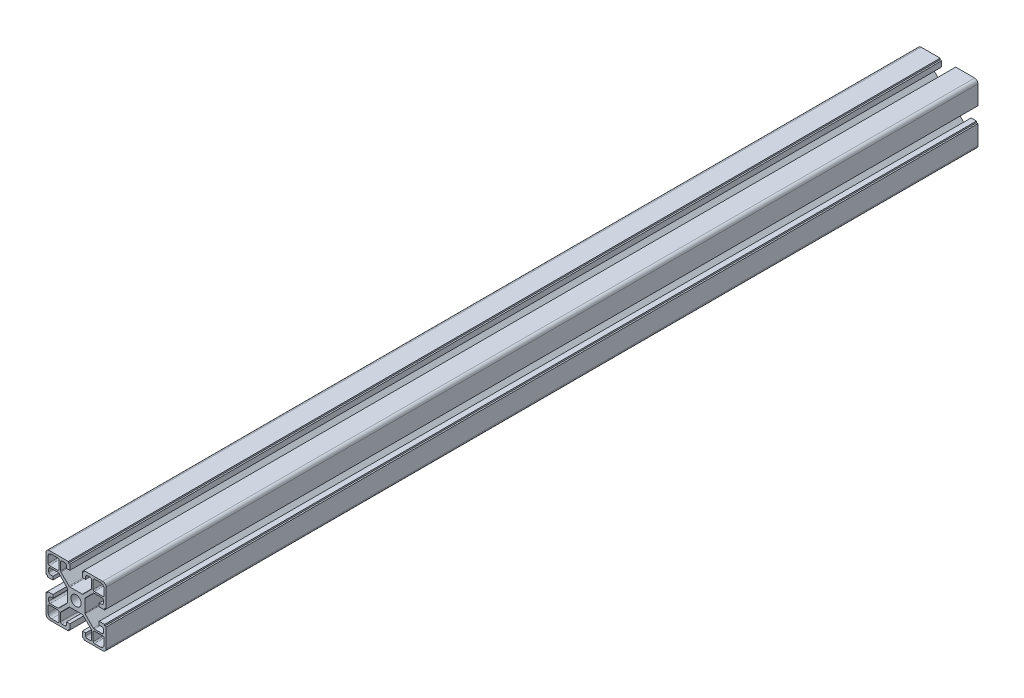
SolidWorks part; units mm, degrees
material "6063-T5"
ref_plane "Front Plane" through (0, 0, 0) normal (0, 0, 1) x (1, 0, 0)
ref_plane "Top Plane" through (0, 0, 0) normal (0, 1, 0) x (1, 0, 0)
ref_plane "Right Plane" through (0, 0, 0) normal (1, 0, 0) x (0, 0, -1)
sketch "Sketch1" plane through (0, 0, 0) normal (0, 0, 1) x (1, 0, 0)
  line L4 (20, 17.75) -> (20, 5.15)
  line L5 (0, -17.7813) -> (0, 18.2) construction
  line L6 (0, 0) -> (38.8613, 0) construction
  line L8 (18.6, 16.35) -> (18.6, 12.2)
  line L10 (11.4, 17.8) -> (11.4, 12.2)
  line L11 (-4.1, 5.85) -> (4.1, 5.85)
  line L14 (5.85, 4.1089) -> (5.85, -4.1089)
  line L17 (12.2, 11.4) -> (17.8, 11.4)
  line L24 (4.15, 19) -> (4.15, 15.4)
  line L25 (4.15, 15.4) -> (6.35, 15.4)
  line L26 (6.35, 15.4) -> (6.35, 16.95)
  line L27 (10.3, 17.2) -> (10.3, 12.0545)
  line L28 (10.0659, 11.489) -> (4.6659, 6.0845)
  line L29 (6.0841, 4.6743) -> (11.4708, 10.0655)
  line L30 (12.0367, 10.3) -> (17.2, 10.3)
  line L31 (18.2, 9.3) -> (18.2, 7.6)
  line L32 (16.95, 6.35) -> (15.4, 6.35)
  line L33 (15.4, 6.35) -> (15.4, 4.15)
  line L34 (15.4, 4.15) -> (19, 4.15)
  line L35 (18.6, 18.6) -> (18.6, -18.6) construction
  line L36 (-18.6, 18.6) -> (18.6, 18.6) construction
  line L37 (-20, 20) -> (20, 20) construction
  line L38 (20, 20) -> (20, -20) construction
  line L40 (7.6, 18.2) -> (9.3, 18.2)
  line L42 (4.15, 19) -> (5.15, 19)
  line L43 (5.15, 19) -> (5.15, 20)
  line L56 (-18.6, 18.6) -> (-18.6, -18.6) construction
  line L57 (-20, 20) -> (-20, -20) construction
  line L60 (5.15, 20) -> (17.75, 20)
  line L91 (-18.6, -18.6) -> (18.6, -18.6) construction
  line L92 (-20, -20) -> (20, -20) construction
  line L93 (12.2, 18.6) -> (16.35, 18.6)
  line L94 (17.9399, 17.9421) -> (20, 20) construction
  line L95 (0, 0) -> (11.4, 11.4094) construction
  line L101 (19, 4.15) -> (19, 5.15)
  line L102 (19, 5.15) -> (20, 5.15)
  line L104 (-5.85, 4.1089) -> (-5.85, -4.1089)
  line L105 (-19, 5.15) -> (-20, 5.15)
  line L106 (-19, 4.15) -> (-19, 5.15)
  line L107 (-12.2, 18.6) -> (-16.35, 18.6)
  line L108 (-5.15, 20) -> (-17.75, 20)
  line L109 (-5.15, 19) -> (-5.15, 20)
  line L110 (-4.15, 19) -> (-5.15, 19)
  line L111 (-7.6, 18.2) -> (-9.3, 18.2)
  line L112 (-15.4, 4.15) -> (-19, 4.15)
  line L113 (-15.4, 6.35) -> (-15.4, 4.15)
  line L114 (-16.95, 6.35) -> (-15.4, 6.35)
  line L115 (-18.2, 9.3) -> (-18.2, 7.6)
  line L116 (-12.0367, 10.3) -> (-17.2, 10.3)
  line L117 (-6.0841, 4.6743) -> (-11.4708, 10.0655)
  line L118 (-10.0659, 11.489) -> (-4.6659, 6.0845)
  line L119 (-10.3, 17.2) -> (-10.3, 12.0545)
  line L120 (-6.35, 15.4) -> (-6.35, 16.95)
  line L121 (-4.15, 15.4) -> (-6.35, 15.4)
  line L122 (-4.15, 19) -> (-4.15, 15.4)
  line L123 (-12.2, 11.4) -> (-17.8, 11.4)
  line L124 (-11.4, 17.8) -> (-11.4, 12.2)
  line L125 (-18.6, 16.35) -> (-18.6, 12.2)
  line L126 (-20, 17.75) -> (-20, 5.15)
  line L127 (-20, -17.75) -> (-20, -5.15)
  line L128 (-18.6, -16.35) -> (-18.6, -12.2)
  line L129 (-11.4, -17.8) -> (-11.4, -12.2)
  line L130 (-12.2, -11.4) -> (-17.8, -11.4)
  line L131 (-4.15, -19) -> (-4.15, -15.4)
  line L132 (-4.15, -15.4) -> (-6.35, -15.4)
  line L133 (-6.35, -15.4) -> (-6.35, -16.95)
  line L134 (-10.3, -17.2) -> (-10.3, -12.0545)
  line L135 (-10.0659, -11.489) -> (-4.6659, -6.0845)
  line L136 (-6.0841, -4.6743) -> (-11.4708, -10.0655)
  line L137 (-12.0367, -10.3) -> (-17.2, -10.3)
  line L138 (-18.2, -9.3) -> (-18.2, -7.6)
  line L139 (-16.95, -6.35) -> (-15.4, -6.35)
  line L140 (-15.4, -6.35) -> (-15.4, -4.15)
  line L141 (-15.4, -4.15) -> (-19, -4.15)
  line L142 (-7.6, -18.2) -> (-9.3, -18.2)
  line L143 (-4.15, -19) -> (-5.15, -19)
  line L144 (-5.15, -19) -> (-5.15, -20)
  line L145 (-5.15, -20) -> (-17.75, -20)
  line L146 (-12.2, -18.6) -> (-16.35, -18.6)
  line L147 (-19, -4.15) -> (-19, -5.15)
  line L148 (-19, -5.15) -> (-20, -5.15)
  line L149 (19, -5.15) -> (20, -5.15)
  line L150 (19, -4.15) -> (19, -5.15)
  line L151 (12.2, -18.6) -> (16.35, -18.6)
  line L152 (5.15, -20) -> (17.75, -20)
  line L153 (5.15, -19) -> (5.15, -20)
  line L154 (4.15, -19) -> (5.15, -19)
  line L155 (7.6, -18.2) -> (9.3, -18.2)
  line L156 (15.4, -4.15) -> (19, -4.15)
  line L157 (15.4, -6.35) -> (15.4, -4.15)
  line L158 (16.95, -6.35) -> (15.4, -6.35)
  line L159 (18.2, -9.3) -> (18.2, -7.6)
  line L160 (12.0367, -10.3) -> (17.2, -10.3)
  line L161 (6.0841, -4.6743) -> (11.4708, -10.0655)
  line L162 (10.0659, -11.489) -> (4.6659, -6.0845)
  line L163 (10.3, -17.2) -> (10.3, -12.0545)
  line L164 (6.35, -15.4) -> (6.35, -16.95)
  line L165 (4.15, -15.4) -> (6.35, -15.4)
  line L166 (4.15, -19) -> (4.15, -15.4)
  line L167 (12.2, -11.4) -> (17.8, -11.4)
  line L168 (-4.1, -5.85) -> (4.1, -5.85)
  line L169 (11.4, -17.8) -> (11.4, -12.2)
  line L170 (18.6, -16.35) -> (18.6, -12.2)
  line L171 (20, -17.75) -> (20, -5.15)
  circle A0 centre (0, 0) radius 3.4
  arc A7 (16.35, 18.6) -> (18.6, 16.35) centre (16.35, 16.35) cw
  arc A8 (20, 17.75) -> (17.75, 20) centre (17.75, 17.75) ccw
  arc A9 (6.35, 16.95) -> (7.6, 18.2) centre (7.6, 16.95) cw
  arc A10 (18.2, 7.6) -> (16.95, 6.35) centre (16.95, 7.6) cw
  arc A11 (17.2, 10.3) -> (18.2, 9.3) centre (17.2, 9.3) cw
  arc A12 (9.3, 18.2) -> (10.3, 17.2) centre (9.3, 17.2) cw
  arc A13 (4.6659, 6.0845) -> (4.1, 5.85) centre (4.1, 6.65) cw
  arc A14 (6.0841, 4.6743) -> (5.85, 4.1089) centre (6.65, 4.1089) ccw
  arc A15 (17.8, 11.4) -> (18.6, 12.2) centre (17.8, 12.2) ccw
  arc A16 (12.2, 18.6) -> (11.4, 17.8) centre (12.2, 17.8) ccw
  arc A17 (11.4, 12.2) -> (12.2, 11.4) centre (12.2, 12.2) ccw
  arc A18 (11.4708, 10.0655) -> (12.0367, 10.3) centre (12.0367, 9.5) cw
  arc A19 (10.3, 12.0545) -> (10.0659, 11.489) centre (9.5, 12.0545) cw
  arc A20 (-10.3, 12.0545) -> (-10.0659, 11.489) centre (-9.5, 12.0545) ccw
  arc A21 (-11.4708, 10.0655) -> (-12.0367, 10.3) centre (-12.0367, 9.5) ccw
  arc A22 (-11.4, 12.2) -> (-12.2, 11.4) centre (-12.2, 12.2) cw
  arc A23 (-12.2, 18.6) -> (-11.4, 17.8) centre (-12.2, 17.8) cw
  arc A24 (-17.8, 11.4) -> (-18.6, 12.2) centre (-17.8, 12.2) cw
  arc A25 (-6.0841, 4.6743) -> (-5.85, 4.1089) centre (-6.65, 4.1089) cw
  arc A26 (-4.6659, 6.0845) -> (-4.1, 5.85) centre (-4.1, 6.65) ccw
  arc A27 (-9.3, 18.2) -> (-10.3, 17.2) centre (-9.3, 17.2) ccw
  arc A28 (-17.2, 10.3) -> (-18.2, 9.3) centre (-17.2, 9.3) ccw
  arc A29 (-18.2, 7.6) -> (-16.95, 6.35) centre (-16.95, 7.6) ccw
  arc A30 (-6.35, 16.95) -> (-7.6, 18.2) centre (-7.6, 16.95) ccw
  arc A31 (-20, 17.75) -> (-17.75, 20) centre (-17.75, 17.75) cw
  arc A32 (-16.35, 18.6) -> (-18.6, 16.35) centre (-16.35, 16.35) ccw
  arc A33 (-16.35, -18.6) -> (-18.6, -16.35) centre (-16.35, -16.35) cw
  arc A34 (-20, -17.75) -> (-17.75, -20) centre (-17.75, -17.75) ccw
  arc A35 (-6.35, -16.95) -> (-7.6, -18.2) centre (-7.6, -16.95) cw
  arc A36 (-18.2, -7.6) -> (-16.95, -6.35) centre (-16.95, -7.6) cw
  arc A37 (-17.2, -10.3) -> (-18.2, -9.3) centre (-17.2, -9.3) cw
  arc A38 (-9.3, -18.2) -> (-10.3, -17.2) centre (-9.3, -17.2) cw
  arc A39 (-4.6659, -6.0845) -> (-4.1, -5.85) centre (-4.1, -6.65) cw
  arc A40 (-6.0841, -4.6743) -> (-5.85, -4.1089) centre (-6.65, -4.1089) ccw
  arc A41 (-17.8, -11.4) -> (-18.6, -12.2) centre (-17.8, -12.2) ccw
  arc A42 (-12.2, -18.6) -> (-11.4, -17.8) centre (-12.2, -17.8) ccw
  arc A43 (-11.4, -12.2) -> (-12.2, -11.4) centre (-12.2, -12.2) ccw
  arc A44 (-11.4708, -10.0655) -> (-12.0367, -10.3) centre (-12.0367, -9.5) cw
  arc A45 (-10.3, -12.0545) -> (-10.0659, -11.489) centre (-9.5, -12.0545) cw
  arc A46 (10.3, -12.0545) -> (10.0659, -11.489) centre (9.5, -12.0545) ccw
  arc A47 (11.4708, -10.0655) -> (12.0367, -10.3) centre (12.0367, -9.5) ccw
  arc A48 (11.4, -12.2) -> (12.2, -11.4) centre (12.2, -12.2) cw
  arc A49 (12.2, -18.6) -> (11.4, -17.8) centre (12.2, -17.8) cw
  arc A50 (17.8, -11.4) -> (18.6, -12.2) centre (17.8, -12.2) cw
  arc A51 (6.0841, -4.6743) -> (5.85, -4.1089) centre (6.65, -4.1089) cw
  arc A52 (4.6659, -6.0845) -> (4.1, -5.85) centre (4.1, -6.65) ccw
  arc A53 (9.3, -18.2) -> (10.3, -17.2) centre (9.3, -17.2) ccw
  arc A54 (17.2, -10.3) -> (18.2, -9.3) centre (17.2, -9.3) ccw
  arc A55 (18.2, -7.6) -> (16.95, -6.35) centre (16.95, -7.6) ccw
  arc A56 (6.35, -16.95) -> (7.6, -18.2) centre (7.6, -16.95) ccw
  arc A57 (20, -17.75) -> (17.75, -20) centre (17.75, -17.75) cw
  arc A58 (16.35, -18.6) -> (18.6, -16.35) centre (16.35, -16.35) ccw
  point P0 (0, 0)
  point P16 (-5.85, 0)
  point P66 (0, 5.85)
  point P120 (5.85, 0)
  point P218 (0, -5.85)
  dimension "D5" = 6.8
  dimension "D6" = 1.4
  dimension "D15" = 5.85
  dimension "D44" = 2.25
  dimension "D25" = 1.25
  dimension "D26" = 1
  dimension "D27" = 0.8
  dimension "D7" = 1.1
  dimension "D8" = 1.1
  dimension "D9" = 1.8
  dimension "D10" = 2.2
  dimension "D11" = 4.6
  dimension "D12" = 1.8
  dimension "D13" = 2.2
  dimension "D14" = 5.85
  dimension "D16" = 1.4
  dimension "D17" = 4.15
  dimension "D18" = 1
  dimension "D19" = 1
  dimension "D20" = 10.3
  dimension "D21" = 4.15
  dimension "D22" = 2
  dimension "D23" = 45.024
  dimension "D24" = 1
  dimension "D41" = 10.3
  dimension "D60" = 14.15
  dimension "D73" = 1
  dimension "D74" = 1
  dimension "D82" = 14.15
  dimension "D3" = 4.6
extrude "Boss-Extrude1" add sketch "Sketch1" along normal blind 713
sketch "Sketch2" plane through (0, 20, 0) normal (0, 1, 0) x (1, 0, 0)
  line L0 (-20, -713) -> (-20, 0) construction
  line L1 (-20, -580) -> (20, -580)
  line L2 (-20, -580) -> (-20, -713)
  line L3 (-20, -713) -> (20, -713)
  line L4 (20, -580) -> (20, -713)
  line L5 (-5.15, 0) -> (-17.75, 0) construction
  dimension "D1" = 580
extrude "Cut-Extrude1" cut sketch "Sketch2" against normal through all
